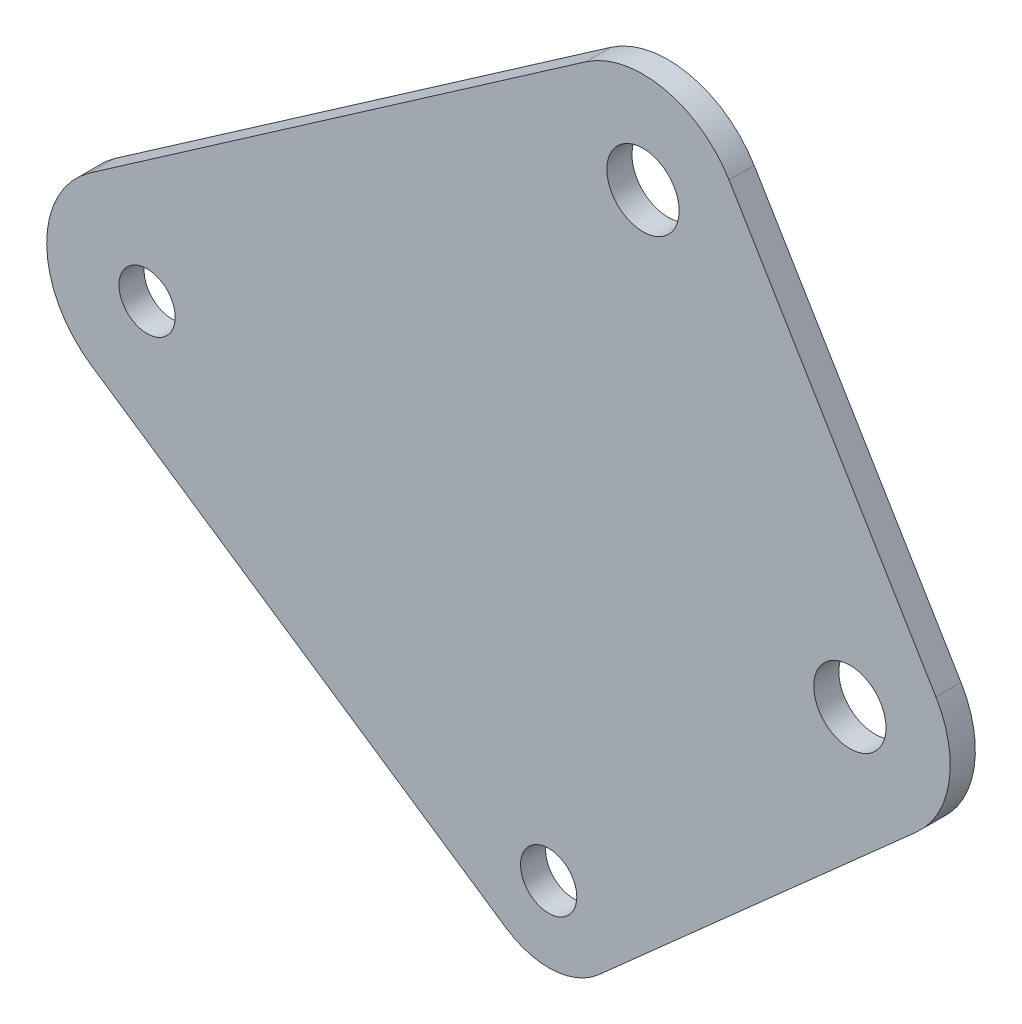
SolidWorks part; units mm, degrees
material "Delrin 2700 NC010, Low Viscosity Acetal Copolymer (SS)"
ref_plane "Front Plane" through (0, 0, 0) normal (0, 0, 1) x (1, 0, 0)
ref_plane "Top Plane" through (0, 0, 0) normal (0, 1, 0) x (1, 0, 0)
ref_plane "Right Plane" through (0, 0, 0) normal (1, 0, 0) x (0, 0, -1)
sketch "Sketch1" plane through (0, 0, 0) normal (0, 0, 1) x (1, 0, 0)
  line L0 (31.367, 21.7714) -> (44.45, 0) construction
  line L1 (27.7462, 26.988) -> (-3.6208, 5.2166)
  line L2 (-3.5512, -5.2641) -> (22.7366, -22.9981)
  line L3 (28.5633, -22.6102) -> (48.6677, -4.7469)
  line L4 (49.8929, 3.2708) -> (36.8099, 25.0422)
  circle A0 centre (0, 0) radius 1.778
  circle A1 centre (44.45, 0) radius 2.286
  circle A2 centre (31.367, 21.7714) radius 2.286
  circle A3 centre (25.4, -19.05) radius 1.778
  arc A4 (-3.6208, 5.2166) -> (-3.5512, -5.2641) centre (0, 0) ccw
  arc A5 (22.7366, -22.9981) -> (28.5633, -22.6102) centre (25.4, -19.05) ccw
  arc A6 (48.6677, -4.7469) -> (49.8929, 3.2708) centre (44.45, 0) ccw
  arc A7 (36.8099, 25.0422) -> (27.7462, 26.988) centre (31.367, 21.7714) ccw
  dimension "D5" = 3.556
  dimension "D6" = 4.572
  dimension "D7" = 38.1
  dimension "D8" = 6.35
  dimension "D9" = 6.35
  dimension "D10" = 6.35
  dimension "D11" = 4.7625
  dimension "D1" = 44.45
  dimension "D2" = 25.4
  dimension "D3" = 25.4
  dimension "D4" = 19.05
extrude "Boss-Extrude1" add sketch "Sketch1" along normal blind 1.5875
